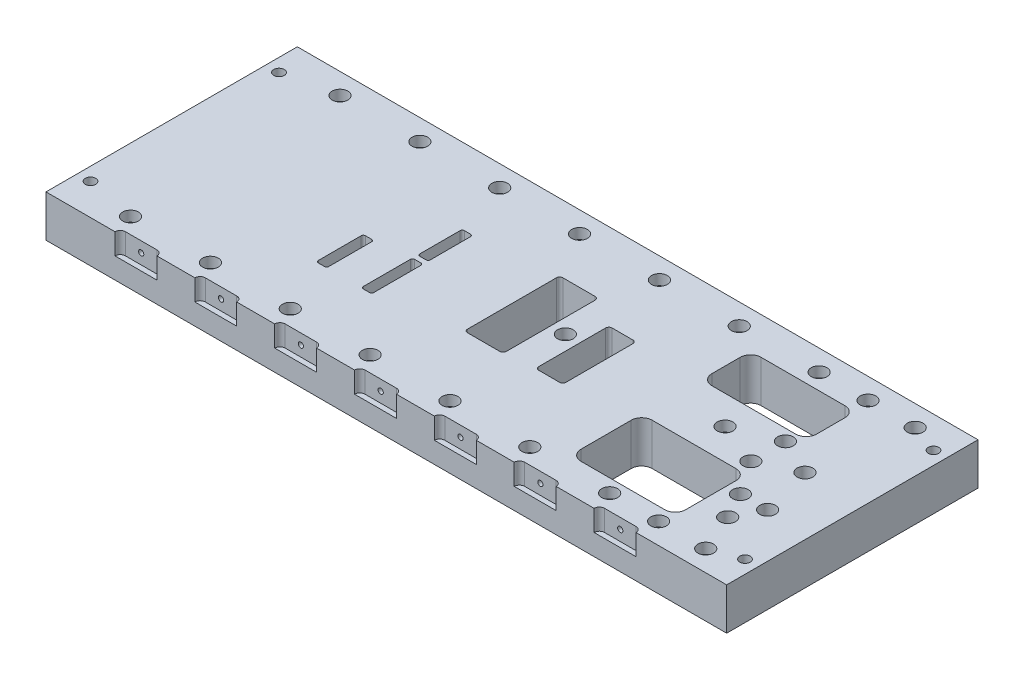
SolidWorks part; units mm, degrees
material "K110"
ref_plane "Front Plane" through (0, 0, 0) normal (0, 0, 1) x (1, 0, 0)
ref_plane "Top Plane" through (0, 0, 0) normal (0, 1, 0) x (1, 0, 0)
ref_plane "Right Plane" through (0, 0, 0) normal (1, 0, 0) x (0, 0, -1)
sketch "Sketch1" plane through (0, 0, 0) normal (0, 1, 0) x (1, 0, 0)
  line L1 (-325, -120) -> (325, -120)
  line L2 (-325, -120) -> (-325, 120)
  line L3 (-325, 120) -> (325, 120)
  line L4 (325, -120) -> (325, 120)
  line L5 (-325, -120) -> (325, 120) construction
  line L6 (-325, 120) -> (325, -120) construction
  point P0 (0, 0)
  dimension "D1" = 240
  dimension "D2" = 650
extrude "Boss-Extrude1" add sketch "Sketch1" against normal blind 40
sketch "Sketch2" plane through (0, 0, 0) normal (0, 1, 0) x (1, 0, 0)
  line L0 (187.25, -63.53) -> (187.25, -47.4) construction
  line L1 (184.25, -44.4) -> (180.25, -44.4) construction
  line L2 (174.25, -38.4) -> (174.25, -32.27) construction
  line L3 (174.25, -32.27) -> (172.25, -32.27) construction
  line L12 (169.25, -35.27) -> (169.25, -71.53) construction
  line L13 (172.25, -74.53) -> (214.25, -74.53) construction
  line L14 (199.25, -47.4) -> (199.25, -63.53) construction
  line L15 (206.25, -44.4) -> (202.25, -44.4) construction
  line L16 (212.25, -32.27) -> (212.25, -38.4) construction
  line L17 (214.25, -32.27) -> (212.25, -32.27) construction
  line L18 (217.25, -71.53) -> (217.25, -35.27) construction
  line L19 (187.25, -63.53) -> (187.25, -47.4)
  line L20 (184.25, -44.4) -> (180.25, -44.4)
  line L21 (174.25, -38.4) -> (174.25, -32.27)
  line L22 (174.25, -32.27) -> (172.25, -32.27)
  line L23 (169.25, -35.27) -> (169.25, -71.53)
  line L24 (172.25, -74.53) -> (214.25, -74.53)
  line L25 (199.25, -47.4) -> (199.25, -63.53)
  line L26 (206.25, -44.4) -> (202.25, -44.4)
  line L27 (212.25, -32.27) -> (212.25, -38.4)
  line L28 (214.25, -32.27) -> (212.25, -32.27)
  line L29 (217.25, -71.53) -> (217.25, -35.27)
  line L30 (212.25, 47.73) -> (214.25, 47.73) construction
  line L31 (212.25, 69.53) -> (212.25, 47.73) construction
  line L32 (174.25, 69.53) -> (212.25, 69.53) construction
  line L33 (174.25, 47.73) -> (174.25, 69.53) construction
  line L34 (172.25, 47.73) -> (174.25, 47.73) construction
  line L35 (169.25, 71.53) -> (169.25, 50.73) construction
  line L36 (214.25, 74.53) -> (172.25, 74.53) construction
  line L37 (217.25, 50.73) -> (217.25, 71.53) construction
  line L38 (212.25, 47.73) -> (214.25, 47.73)
  line L39 (212.25, 69.53) -> (212.25, 47.73)
  line L40 (174.25, 69.53) -> (212.25, 69.53)
  line L41 (174.25, 47.73) -> (174.25, 69.53)
  line L42 (172.25, 47.73) -> (174.25, 47.73)
  line L43 (169.25, 71.53) -> (169.25, 50.73)
  line L44 (214.25, 74.53) -> (172.25, 74.53)
  line L45 (217.25, 50.73) -> (217.25, 71.53)
  arc A0 (187.25, -47.4) -> (184.25, -44.4) centre (184.25, -47.4) ccw construction
  arc A1 (174.25, -38.4) -> (180.25, -44.4) centre (180.25, -38.4) ccw construction
  arc A2 (172.25, -32.27) -> (169.25, -35.27) centre (172.25, -35.27) ccw construction
  arc A3 (169.25, -71.53) -> (172.25, -74.53) centre (172.25, -71.53) ccw construction
  arc A4 (214.25, -74.53) -> (217.25, -71.53) centre (214.25, -71.53) ccw construction
  arc A5 (187.25, -63.53) -> (199.25, -63.53) centre (193.25, -63.53) ccw construction
  arc A6 (202.25, -44.4) -> (199.25, -47.4) centre (202.25, -47.4) ccw construction
  arc A7 (206.25, -44.4) -> (212.25, -38.4) centre (206.25, -38.4) ccw construction
  arc A8 (217.25, -35.27) -> (214.25, -32.27) centre (214.25, -35.27) ccw construction
  arc A9 (187.25, -47.4) -> (184.25, -44.4) centre (184.25, -47.4) ccw
  arc A10 (174.25, -38.4) -> (180.25, -44.4) centre (180.25, -38.4) ccw
  arc A11 (172.25, -32.27) -> (169.25, -35.27) centre (172.25, -35.27) ccw
  arc A12 (169.25, -71.53) -> (172.25, -74.53) centre (172.25, -71.53) ccw
  arc A13 (214.25, -74.53) -> (217.25, -71.53) centre (214.25, -71.53) ccw
  arc A14 (187.25, -63.53) -> (199.25, -63.53) centre (193.25, -63.53) ccw
  arc A15 (202.25, -44.4) -> (199.25, -47.4) centre (202.25, -47.4) ccw
  arc A16 (206.25, -44.4) -> (212.25, -38.4) centre (206.25, -38.4) ccw
  arc A17 (217.25, -35.27) -> (214.25, -32.27) centre (214.25, -35.27) ccw
  circle A18 centre (269.5, -63.53) radius 2.5 construction
  circle A19 centre (282.5, -38.4) radius 2.5 construction
  circle A20 centre (256.5, -38.4) radius 2.5 construction
  circle A21 centre (234.38, -6.27) radius 2.5 construction
  circle A22 centre (234.38, 26.73) radius 2.5 construction
  arc A23 (214.25, 47.73) -> (217.25, 50.73) centre (214.25, 50.73) ccw construction
  arc A24 (169.25, 50.73) -> (172.25, 47.73) centre (172.25, 50.73) ccw construction
  arc A25 (172.25, 74.53) -> (169.25, 71.53) centre (172.25, 71.53) ccw construction
  arc A26 (217.25, 71.53) -> (214.25, 74.53) centre (214.25, 71.53) ccw construction
  circle A27 centre (269.5, -63.53) radius 2.5
  circle A28 centre (282.5, -38.4) radius 2.5
  circle A29 centre (256.5, -38.4) radius 2.5
  circle A30 centre (234.38, -6.27) radius 2.5
  circle A31 centre (234.38, 26.73) radius 2.5
  arc A32 (214.25, 47.73) -> (217.25, 50.73) centre (214.25, 50.73) ccw
  arc A33 (169.25, 50.73) -> (172.25, 47.73) centre (172.25, 50.73) ccw
  arc A34 (172.25, 74.53) -> (169.25, 71.53) centre (172.25, 71.53) ccw
  arc A35 (217.25, 71.53) -> (214.25, 74.53) centre (214.25, 71.53) ccw
sketch "Sketch3" plane through (0, 0, 0) normal (0, 1, 0) x (1, 0, 0)
  line L1 (153.25, 84.63) -> (233.25, 84.63)
  line L2 (143.25, 74.63) -> (143.25, 47.63)
  line L3 (153.25, 37.63) -> (233.25, 37.63)
  line L4 (243.25, 74.63) -> (243.25, 47.63)
  line L8 (169.25, -53.4) -> (217.25, -53.4) construction
  line L9 (153.25, -19.4) -> (233.25, -19.4)
  line L10 (143.25, -29.4) -> (143.25, -77.4)
  line L11 (153.25, -87.4) -> (233.25, -87.4)
  line L12 (243.25, -29.4) -> (243.25, -77.4)
  line L13 (169.25, -35.27) -> (169.25, -71.53) construction
  line L14 (217.25, -71.53) -> (217.25, -35.27) construction
  line L15 (193.25, -74.53) -> (193.25, -19.4) construction
  line L16 (172.25, -74.53) -> (214.25, -74.53) construction
  line L17 (193.25, 84.63) -> (193.25, 47.73) construction
  line L18 (169.25, 61.13) -> (217.25, 61.13) construction
  line L19 (169.25, 71.53) -> (169.25, 50.73) construction
  line L20 (217.25, 50.73) -> (217.25, 71.53) construction
  arc A0 (143.25, 47.63) -> (153.25, 37.63) centre (153.25, 47.63) ccw
  arc A1 (233.25, 37.63) -> (243.25, 47.63) centre (233.25, 47.63) ccw
  arc A2 (243.25, 74.63) -> (233.25, 84.63) centre (233.25, 74.63) ccw
  arc A3 (153.25, 84.63) -> (143.25, 74.63) centre (153.25, 74.63) ccw
  circle A4 centre (234.38, 26.73) radius 7.5
  circle A5 centre (234.38, -6.27) radius 7.5
  circle A6 centre (269.5, -63.53) radius 7.5
  circle A7 centre (282.5, -38.4) radius 7.5
  circle A8 centre (256.5, -38.4) radius 7.5
  arc A9 (143.25, -77.4) -> (153.25, -87.4) centre (153.25, -77.4) ccw
  arc A10 (233.25, -87.4) -> (243.25, -77.4) centre (233.25, -77.4) ccw
  arc A11 (243.25, -29.4) -> (233.25, -19.4) centre (233.25, -29.4) ccw
  arc A12 (153.25, -19.4) -> (143.25, -29.4) centre (153.25, -29.4) ccw
  dimension "D5" = 10
  dimension "D6" = 15
  dimension "D11" = 10
  dimension "D2" = 100
  dimension "D3" = 47
  dimension "D7" = 68
  dimension "D8" = 100
extrude "Cut-Extrude2" cut sketch "Sketch3" against normal up to next
sketch "Sketch4" plane through (0, -40, 0) normal (0, -1, 0) x (1, 0, 0)
  circle A0 centre (234.38, -26.73) radius 9
  circle A1 centre (234.38, 6.27) radius 9
  circle A2 centre (256.5, 38.4) radius 9
  circle A3 centre (282.5, 38.4) radius 9
  circle A4 centre (269.5, 63.53) radius 9
  dimension "D1" = 18
extrude "Cut-Extrude3" cut sketch "Sketch4" against normal blind 5
extrude "Cut-Extrude9" cut sketch "Sketch11" against normal through all
sketch "Sketch11" plane through (304.63, 0, 0) normal (0, 1, 0) x (1, 0, 0)
  circle A0 centre (-35.13, 10.23) radius 7.5
  circle A1 centre (-111.38, 10.23) radius 7.5
  circle A2 centre (-263.88, 10.23) radius 7.5
extrude "Cut-Extrude10" cut sketch "Sketch12" against normal blind 5
sketch "Sketch12" plane through (304.63, -40, 0) normal (0, -1, 0) x (1, 0, 0)
  circle A0 centre (-35.13, -10.23) radius 10
extrude "Cut-Extrude11" cut sketch "Sketch13" against normal blind 30
sketch "Sketch13" plane through (304.63, -40, 0) normal (0, -1, 0) x (1, 0, 0)
  circle A0 centre (-111.38, -10.23) radius 10
  circle A4 centre (-263.88, -10.23) radius 7.5 construction
  circle A5 centre (-263.88, -10.23) radius 10
hole_wizard "M10 Tapped Hole1" positions "Sketch27" profile "Sketch15" tap size "M10" standard "ISO"
sketch "Sketch27" plane through (0, -40, 0) normal (0, -1, 0) x (-1, 0, 0)
  line L0 (-325, -120) -> (-325, 120) construction
  line L1 (-325, 120) -> (325, 120) construction
  line L2 (325, 120) -> (325, -120) construction
  line L3 (325, -120) -> (-325, -120) construction
  point P0 (-312.5, 107.5)
  point P2 (312.5, 107.5)
  point P4 (312.5, -107.5)
  point P6 (-312.5, -107.5)
  dimension "D1" = 12.5
  dimension "D2" = 12.5
  dimension "D3" = 12.5
  dimension "D4" = 12.5
sketch "Sketch15" plane through (312.5, -40, -107.5) normal (1, 0, 0) x (0, 0, -1)
  line L0 (0, 0) -> (0, 30.0537)
  line L1 (0, 30.0537) -> (4.25, 27.5)
  line L2 (4.25, 27.5) -> (4.25, 0.775)
  line L3 (4.25, 0.775) -> (5.025, 0)
  line L5 (5.025, 0) -> (0, 0)
  line L6 (-4.25, 0.775) -> (-5.025, 0) construction
  line L10 (0, 30.0537) -> (-4.25, 27.5) construction
  line L11 (0, -6.35) -> (0, 107.95) construction
  dimension "Tap Drill Dia." = 8.5
  dimension "Tap Drill Depth" = 27.5
  dimension "Near C'Sink Dia." = 10.05
  dimension "Near C'Sink Angle" = 90
  dimension "Drill Angle" = 118
cosmetic thread "Hole Thread1" parameters "D1"=20, "D2"=10
cosmetic thread "Hole Thread2" parameters "D1"=20, "D2"=10
cosmetic thread "Hole Thread3" parameters "D1"=20, "D2"=10
cosmetic thread "Hole Thread4" parameters "D1"=20, "D2"=10
hole_wizard "Ø10.0mm Dowel Hole2" positions "Sketch26" profile "Sketch25" hole size "Ø10.0" standard "ISO" end condition through all
sketch "Sketch26" plane through (0, -40, 0) normal (0, -1, 0) x (-1, 0, 0)
  line L0 (-325, -120) -> (-325, 120) construction
  line L1 (325, 120) -> (325, -120) construction
  circle A0 centre (-312.5, 107.5) radius 4.25 construction
  circle A1 centre (-312.5, -107.5) radius 4.25 construction
  point P0 (-312.5, 90)
  point P2 (312.5, 90)
  point P4 (312.5, -90)
  point P6 (-312.5, -90)
  dimension "D4" = 17.5
  dimension "D1" = 12.5
  dimension "D2" = 17.5
  dimension "D3" = 12.5
sketch "Sketch25" plane through (312.5, -40, -90) normal (1, 0, 0) x (0, 0, -1)
  line L0 (0, 0) -> (0, 40)
  line L1 (0, 40) -> (5, 40)
  line L2 (5, 40) -> (5, 0)
  line L5 (5, 0) -> (0, 0)
  line L11 (0, -6.35) -> (0, 107.95) construction
  dimension "Thru Hole Dia." = 10
  dimension "Thru Hole Depth" = 40
sketch "Sketch28" plane through (0, 0, 0) normal (0, 1, 0) x (1, 0, 0)
  line L0 (-315.37, -95) -> (304.63, -95) construction
  line L2 (325, -120) -> (325, 120) construction
  circle A0 centre (240, -100) radius 7.5
  circle A1 centre (285, -100) radius 7.5
  circle A2 centre (117, -100) radius 7.5
  circle A3 centre (40.75, -100) radius 7.5
  circle A4 centre (193.25, -100) radius 7.5
  circle A5 centre (-35.5, -100) radius 7.5
  circle A6 centre (-111.75, -100) radius 7.5
  circle A7 centre (-188, -100) radius 7.5
  circle A8 centre (-264.25, -100) radius 7.5
  dimension "D1" = 15
  dimension "D2" = 5
  dimension "D3" = 46.75
  dimension "D4" = 40
  dimension "D5" = 45
  dimension "D7" = 76.25
  dimension "D6" = 7
extrude "Cut-Extrude12" cut sketch "Sketch28" against normal up to next
mirror "Mirror1" about plane through (0, 0, 0) normal (0, 0, 1) of "Cut-Extrude12"
sketch "Sketch29" plane through (0, -40, 0) normal (0, -1, 0) x (1, 0, 0)
  circle A0 centre (193.25, 100) radius 9
  circle A1 centre (240, 100) radius 9
  circle A2 centre (240, -100) radius 9
  circle A3 centre (193.25, -100) radius 9
  circle A4 centre (285, 100) radius 9
  circle A5 centre (285, -100) radius 9
  circle A6 centre (117, 100) radius 9
  circle A7 centre (117, -100) radius 9
  circle A8 centre (40.75, 100) radius 9
  circle A9 centre (40.75, -100) radius 9
  circle A10 centre (-35.5, 100) radius 9
  circle A11 centre (-35.5, -100) radius 9
  circle A12 centre (-111.75, 100) radius 9
  circle A13 centre (-111.75, -100) radius 9
  circle A14 centre (-188, 100) radius 9
  circle A15 centre (-188, -100) radius 9
  circle A16 centre (-264.25, 100) radius 9
  circle A17 centre (-264.25, -100) radius 9
  dimension "D1" = 18
  dimension "D2" = 7
extrude "Cut-Extrude13" cut sketch "Sketch29" against normal blind 30
extrude "Cut-Extrude14" cut sketch "Sketch30" against normal blind 20
sketch "Sketch30" plane through (304.63, 0, 0) normal (0, 1, 0) x (1, 0, 0)
  line L1 (-106.25, -120) -> (-66.25, -120)
  line L3 (-101.25, -115) -> (-71.25, -115)
  arc A0 (-106.25, -120) -> (-101.25, -115) centre (-101.25, -120) cw
  arc A1 (-66.25, -120) -> (-71.25, -115) centre (-71.25, -120) ccw
hole_wizard "M6 Tapped Hole1" positions "Sketch37" profile "Sketch32" tap size "M6" standard "ISO"
sketch "Sketch37" plane through (0, 0, 115) normal (0, 0, 1) x (1, 0, 0)
  line L4 (218.38, -20) -> (218.38, 0) construction
  line L5 (198.38, -20) -> (238.38, -20) construction
  line L6 (233.38, 0) -> (203.38, 0) construction
  line L7 (132, 0) -> (-132, 0) construction
  point P2 (218.38, -10)
  dimension "D1" = 10
sketch "Sketch32" plane through (218.38, -10, 115) normal (1, 0, 0) x (0, -1, 0)
  line L0 (0, 0) -> (0, 11.5022)
  line L1 (0, 11.5022) -> (2.5, 10)
  line L2 (2.5, 10) -> (2.5, 0)
  line L5 (2.5, 0) -> (0, 0)
  line L10 (0, 11.5022) -> (-2.5, 10) construction
  line L11 (0, -6.35) -> (0, 107.95) construction
  dimension "Tap Drill Dia." = 5
  dimension "Tap Drill Depth" = 10
  dimension "Drill Angle" = 118
cosmetic thread "Hole Thread5" parameters "D1"=8, "D2"=6
pattern_linear "LPattern1" count 7 spacing 76.25 along (-1, 0, 0) of "M6 Tapped Hole1", "Cut-Extrude14"
cosmetic thread "Hole Thread6" parameters "D1"=8, "D2"=6
cosmetic thread "Hole Thread7" parameters "D1"=8, "D2"=6
cosmetic thread "Hole Thread8" parameters "D1"=8, "D2"=6
cosmetic thread "Hole Thread9" parameters "D1"=8, "D2"=6
cosmetic thread "Hole Thread10" parameters "D1"=8, "D2"=6
cosmetic thread "Hole Thread11" parameters "D1"=8, "D2"=6
sketch "Sketch38" plane through (0, 0, 0) normal (0, 1, 0) x (1, 0, 0)
  line L0 (75.88, -10.27) -> (75.88, 15.73) construction
  line L1 (57.75, -32.27) -> (77.75, -32.27)
  line L2 (54.75, -29.27) -> (54.75, 34.73)
  line L3 (57.75, 37.73) -> (77.75, 37.73)
  line L4 (80.75, -29.27) -> (80.75, 34.73)
  line L5 (72.88, 18.73) -> (59.75, 18.73) construction
  line L6 (59.75, -11.27) -> (59.75, -13.27) construction
  line L7 (59.75, -13.27) -> (72.88, -13.27) construction
  arc A1 (57.75, -32.27) -> (54.75, -29.27) centre (57.75, -29.27) cw
  arc A2 (77.75, -32.27) -> (80.75, -29.27) centre (77.75, -29.27) ccw
  arc A3 (77.75, 37.73) -> (80.75, 34.73) centre (77.75, 34.73) cw
  arc A4 (54.75, 34.73) -> (57.75, 37.73) centre (57.75, 34.73) cw
  point P18 (80.75, 37.73)
  point P21 (54.75, 37.73)
  dimension "D7" = 3
  dimension "D1" = 4.87
  dimension "D2" = 19
  dimension "D3" = 5
  dimension "D4" = 19
  dimension "D5" = 70
  dimension "D6" = 26
extrude "Cut-Extrude15" cut sketch "Sketch38" against normal up to next
sketch "Sketch39" plane through (0, 0, 0) normal (0, 1, 0) x (1, 0, 0)
  line L0 (-5.37, 11.73) -> (-5.37, -6.27) construction
  line L1 (-7.25, -35.27) -> (23.75, -35.27)
  line L2 (-10.25, -32.27) -> (-10.25, 52.73)
  line L3 (-7.25, 55.73) -> (23.75, 55.73)
  line L4 (26.75, -32.27) -> (26.75, 52.73)
  line L5 (21.75, -17.27) -> (21.75, -13.77) construction
  line L6 (-2.37, -17.27) -> (21.75, -17.27) construction
  line L7 (21.75, 37.73) -> (-2.37, 37.73) construction
  arc A0 (23.75, 55.73) -> (26.75, 52.73) centre (23.75, 52.73) cw
  arc A1 (-10.25, 52.73) -> (-7.25, 55.73) centre (-7.25, 52.73) cw
  arc A2 (-7.25, -35.27) -> (-10.25, -32.27) centre (-7.25, -32.27) cw
  arc A3 (23.75, -35.27) -> (26.75, -32.27) centre (23.75, -32.27) ccw
  point P14 (26.75, 55.73)
  point P17 (-10.25, 55.73)
  point P22 (26.75, -35.27)
  dimension "D7" = 3
  dimension "D1" = 4.88
  dimension "D2" = 5
  dimension "D3" = 18
  dimension "D4" = 18
  dimension "D5" = 91
  dimension "D6" = 37
extrude "Cut-Extrude16" cut sketch "Sketch39" against normal up to next
sketch "Sketch40" plane through (0, 0, 0) normal (0, 1, 0) x (1, 0, 0)
  line L0 (-90.25, -36.27) -> (-90.25, -12.27) construction
  line L13 (-92.75, -36.27) -> (-92.75, -12.27) construction
  line L14 (-87.75, -36.27) -> (-87.75, -12.27) construction
  line L15 (-90.25, -24.27) -> (-85.25, -24.27) construction
  line L16 (-92.75, -13.27) -> (-87.75, -13.27) construction
  line L17 (-92.75, -38.4) -> (-92.75, -11.27) construction
  line L18 (-87.75, -71.53) -> (-87.75, -13.27) construction
  line L19 (-133.25, -36.27) -> (-133.25, -16.27) construction
  line L20 (-135.75, -36.27) -> (-135.75, -16.27) construction
  line L21 (-130.75, -36.27) -> (-130.75, -16.27) construction
  line L22 (-135.75, -17.27) -> (-135.75, -35.27) construction
  line L23 (-130.75, -13.77) -> (-130.75, -38.4) construction
  line L24 (-130.75, -17.27) -> (-135.75, -17.27) construction
  line L25 (-90.25, 35.23) -> (-90.25, 17.73) construction
  line L26 (-87.75, 35.23) -> (-87.75, 17.73) construction
  line L27 (-92.75, 35.23) -> (-92.75, 17.73) construction
  line L28 (-92.75, 18.73) -> (-87.75, 18.73) construction
  line L29 (-92.75, 16.73) -> (-92.75, 69.53) construction
  line L30 (-93.25, -48.77) -> (-87.25, -48.77)
  line L31 (-95.25, -46.77) -> (-95.25, -1.77)
  line L32 (-93.25, 0.23) -> (-87.25, 0.23)
  line L33 (-85.25, -46.77) -> (-85.25, -1.77)
  line L34 (-133.25, -26.27) -> (-128.25, -26.27) construction
  line L35 (-136.25, -48.77) -> (-130.25, -48.77)
  line L36 (-138.25, -46.77) -> (-138.25, -5.77)
  line L37 (-136.25, -3.77) -> (-130.25, -3.77)
  line L38 (-128.25, -46.77) -> (-128.25, -5.77)
  line L39 (-90.25, 26.48) -> (-85.25, 26.48) construction
  line L40 (-93.25, 5.23) -> (-87.25, 5.23)
  line L41 (-95.25, 7.23) -> (-95.25, 45.73)
  line L42 (-93.25, 47.73) -> (-87.25, 47.73)
  line L43 (-85.25, 7.23) -> (-85.25, 45.73)
  arc A4 (-92.75, -36.27) -> (-87.75, -36.27) centre (-90.25, -36.27) ccw construction
  arc A5 (-87.75, -12.27) -> (-92.75, -12.27) centre (-90.25, -12.27) ccw construction
  arc A6 (-135.75, -36.27) -> (-130.75, -36.27) centre (-133.25, -36.27) ccw construction
  arc A7 (-130.75, -16.27) -> (-135.75, -16.27) centre (-133.25, -16.27) ccw construction
  arc A8 (-87.75, 35.23) -> (-92.75, 35.23) centre (-90.25, 35.23) ccw construction
  arc A9 (-92.75, 17.73) -> (-87.75, 17.73) centre (-90.25, 17.73) ccw construction
  arc A10 (-93.25, -48.77) -> (-95.25, -46.77) centre (-93.25, -46.77) cw
  arc A11 (-87.25, -48.77) -> (-85.25, -46.77) centre (-87.25, -46.77) ccw
  arc A12 (-87.25, 0.23) -> (-85.25, -1.77) centre (-87.25, -1.77) cw
  arc A13 (-95.25, -1.77) -> (-93.25, 0.23) centre (-93.25, -1.77) cw
  arc A14 (-87.25, 5.23) -> (-85.25, 7.23) centre (-87.25, 7.23) ccw
  arc A15 (-93.25, 5.23) -> (-95.25, 7.23) centre (-93.25, 7.23) cw
  arc A16 (-87.25, 47.73) -> (-85.25, 45.73) centre (-87.25, 45.73) cw
  arc A17 (-95.25, 45.73) -> (-93.25, 47.73) centre (-93.25, 45.73) cw
  arc A18 (-138.25, -5.77) -> (-136.25, -3.77) centre (-136.25, -5.77) cw
  arc A19 (-130.25, -3.77) -> (-128.25, -5.77) centre (-130.25, -5.77) cw
  arc A20 (-136.25, -48.77) -> (-138.25, -46.77) centre (-136.25, -46.77) cw
  arc A21 (-130.25, -48.77) -> (-128.25, -46.77) centre (-130.25, -46.77) ccw
  point P2 (-90.25, -24.27)
  point P13 (-90.25, 26.48)
  point P22 (-133.25, -26.27)
  point P52 (-85.25, 0.23)
  point P55 (-95.25, 0.23)
  point P74 (-85.25, 47.73)
  point P77 (-95.25, 47.73)
  point P80 (-138.25, -3.77)
  point P83 (-128.25, -3.77)
  dimension "D8" = 10
  dimension "D9" = 2
  dimension "D11" = 10
  dimension "D12" = 10
  dimension "D14" = 2
  dimension "D15" = 2
  dimension "D1" = 1
  dimension "D2" = 1
  dimension "D3" = 24
  dimension "D4" = 1
  dimension "D5" = 1
  dimension "D6" = 1
  dimension "D7" = 10
  dimension "D10" = 10
  dimension "D13" = 10
  dimension "D16" = 20
  dimension "D17" = 17.5
extrude "Cut-Extrude17" cut sketch "Sketch40" against normal up to next
